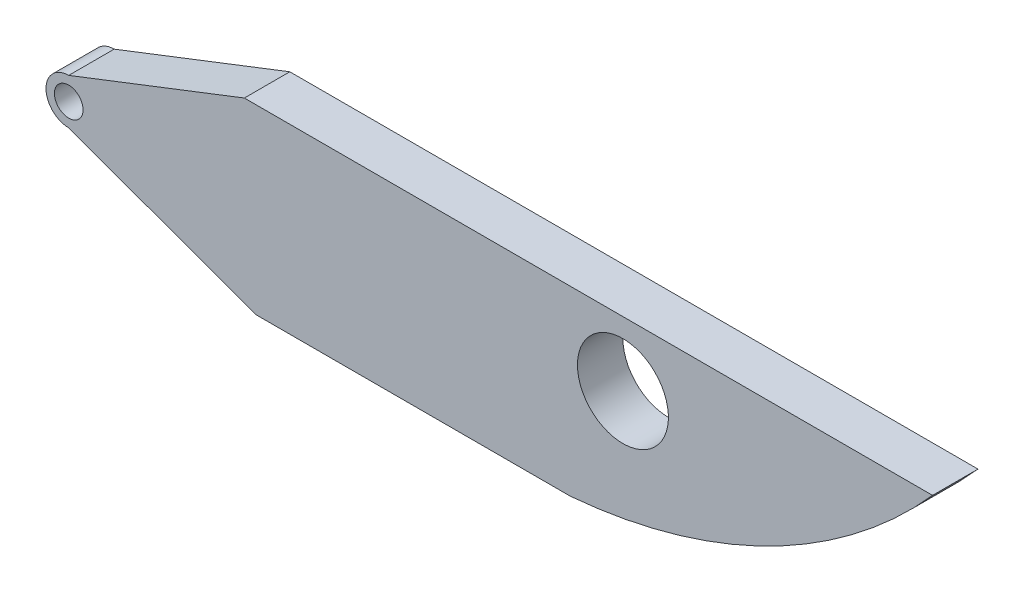
SolidWorks part; units mm, degrees
ref_plane "Front Plane" through (0, 0, 0) normal (0, 0, 1) x (1, 0, 0)
ref_plane "Top Plane" through (0, 0, 0) normal (0, 1, 0) x (1, 0, 0)
ref_plane "Right Plane" through (0, 0, 0) normal (1, 0, 0) x (0, 0, -1)
sketch "Sketch1" plane through (0, 0, 0) normal (0, 0, 1) x (1, 0, 0)
  line L1 (127, 25.4) -> (-127, 25.4)
  line L2 (127, 25.4) -> (127, -25.4)
  line L3 (127, -25.4) -> (-127, -25.4)
  line L4 (-127, 25.4) -> (-127, -25.4)
  line L5 (127, 25.4) -> (-127, -25.4) construction
  line L6 (127, -25.4) -> (-127, 25.4) construction
  point P0 (0, 0)
  dimension "D1" = 254
  dimension "D2" = 50.8
extrude "Boss-Extrude1" add sketch "Sketch1" along normal blind 12.7
sketch "Sketch3" plane through (0, 0, 12.7) normal (0, 0, 1) x (1, 0, 0)
  line L0 (0, 0) -> (-127, 0) construction
  line L1 (-127, 25.4) -> (-127, -25.4) construction
  circle A0 centre (-114.3, 0) radius 4
  dimension "D2" = 8
  dimension "D1" = 12.7
extrude "Cut-Extrude1" cut sketch "Sketch3" against normal through all
sketch "Sketch5" plane through (0, 0, 12.7) normal (0, 0, 1) x (1, 0, 0)
  line L0 (-127, -25.4) -> (127, -25.4) construction
  line L1 (-114.3, -6.35) -> (-62.0461, -25.4)
  line L2 (-114.3, 6.35) -> (-65.2393, 25.4)
  line L3 (127, 25.4) -> (-127, 25.4) construction
  line L4 (-65.2393, 25.4) -> (-127, 25.4)
  line L5 (-127, 25.4) -> (-127, -25.4)
  line L6 (-127, -25.4) -> (-62.0461, -25.4)
  line L7 (127, 25.4) -> (127, -25.4)
  line L8 (127, -25.4) -> (0, -25.4)
  arc A0 (0, -25.4) -> (127, 25.4) centre (12.9194, 126.4514) ccw
  arc A2 (-114.3, 6.35) -> (-114.3, -6.35) centre (-114.3, 0) ccw
  line M3 (-127, 25.4) -> (-127, -25.4)
  line M4 (-127, -25.4) -> (127, -25.4)
  line M5 (127, -25.4) -> (127, 25.4)
  line M6 (127, 25.4) -> (-127, 25.4)
  dimension "D1" = 152.4
  dimension "D2" = 12.7
extrude "Cut-Extrude2" cut sketch "Sketch5" against normal through all contours A0 L8 M5 | A2 L2 L1 M6 M3 M4 region at (-88.4555, -16.6497, 12.7) region at (100.3711, -10.6364, 12.7)
sketch "Sketch6" plane through (0, 0, 12.7) normal (0, 0, 1) x (1, 0, 0)
  line L0 (-114.3, 0) -> (97.983, 0) construction
  arc A0 (25.8389, -25.4) -> (127, 25.4) centre (12.9194, 126.4514) ccw construction
  circle A1 centre (12.7, 0) radius 3.1347
  dimension "D1" = 127
sketch "Sketch7" plane through (0, 0, 0) normal (0, 0, -1) x (-1, 0, 0)
  line L0 (44.0204, -2.9977) -> (44.0204, 16.0523) construction
  point P3 (44.0204, -2.9977)
  point P4 (44.0204, 16.0523)
  dimension "D1" = 19.05
sketch "Sketch11" plane through (0, 0, 0) normal (0, 0, -1) x (-1, 0, 0)
  circle A1 centre (-40.5097, 7.3783) radius 12.7
  dimension "D1" = 25.4
extrude "Cut-Extrude3" cut sketch "Sketch11" against normal through all
